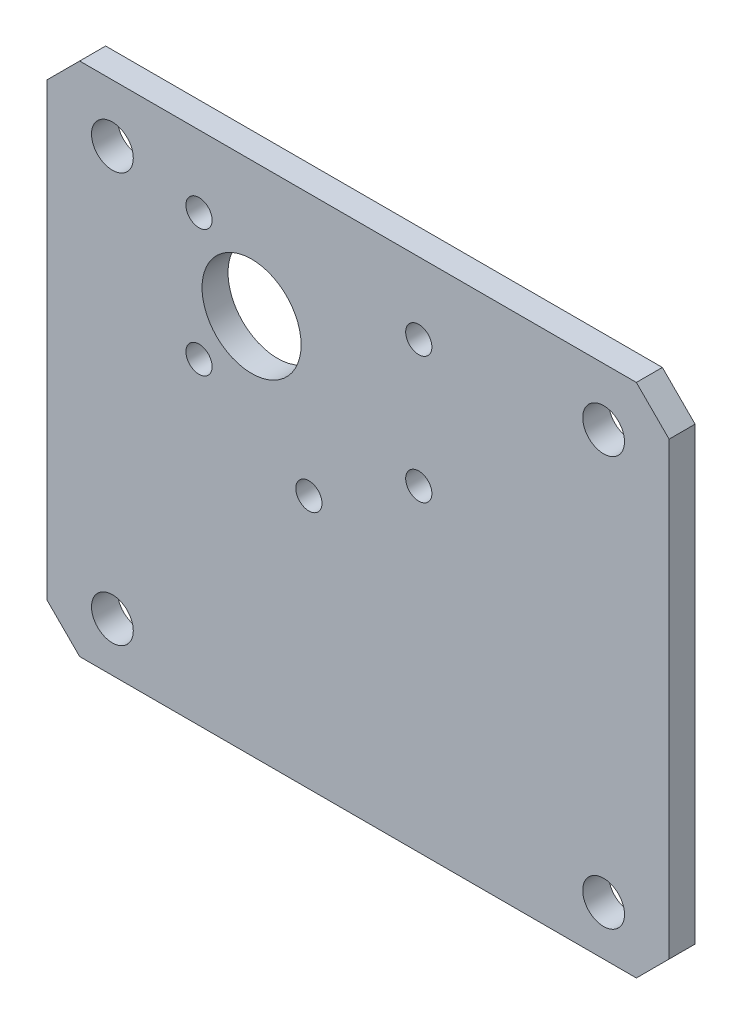
SolidWorks part; units mm, degrees
material "6061-T6 (SS)"
ref_plane "Front" through (0, 0, 0) normal (0, 0, 1) x (1, 0, 0)
ref_plane "Top" through (0, 0, 0) normal (0, 1, 0) x (1, 0, 0)
ref_plane "Right" through (0, 0, 0) normal (1, 0, 0) x (0, 0, -1)
ref_axis "side-side" through (80.9, 0, 0) along (-1, 0, 0)
ref_axis "up-down" through (0, 50, 0) along (0, -1, 0)
ref_axis "front-back" through (0, 0, -80.9) along (0, 0, 1)
sketch "Sketch1" plane through (0, 0, 0) normal (0, 0, 1) x (1, 0, 0)
  line L1 (-32, 16.5) -> (44, 16.5)
  line L2 (-32, 16.5) -> (-32, -46.5)
  line L3 (-32, -46.5) -> (44, -46.5)
  line L4 (44, 16.5) -> (44, -46.5)
  line L5 (0, -50) -> (0, 50) construction
  circle A0 centre (0, 0) radius 18.5 construction
  circle A1 centre (0, 0) radius 18.5 construction
  circle A2 centre (0, 15.5) radius 1.25 construction
  circle A3 centre (0, -15.5) radius 1.25 construction
  circle A4 centre (13.4234, -7.75) radius 1.25 construction
  circle A5 centre (13.4234, 7.75) radius 1.25 construction
  circle A6 centre (0, 15.5) radius 1.25 construction
  circle A7 centre (0, -15.5) radius 1.25 construction
  circle A8 centre (13.4234, -7.75) radius 1.25 construction
  circle A9 centre (13.4234, 7.75) radius 1.25 construction
  circle A10 centre (-13.4234, -7.75) radius 1.25 construction
  circle A11 centre (-13.4234, -7.75) radius 1.25 construction
  circle A12 centre (-13.4234, 7.75) radius 1.25 construction
  circle A13 centre (-13.4234, 7.75) radius 1.25 construction
  circle A14 centre (-7, 0) radius 6.05
  circle A15 centre (-7, 0) radius 6 construction
  circle A16 centre (-13.4234, 7.75) radius 1.6
  circle A17 centre (-13.4234, -7.75) radius 1.6
  circle A18 centre (0, -15.5) radius 1.6
  circle A19 centre (13.4234, -7.75) radius 1.6
  circle A20 centre (13.4234, 7.75) radius 1.6
  circle A21 centre (0, 15.5) radius 1.6 construction
  point P39 (-24, 9.5)
  point P40 (-24, -40.5)
  point P41 (36, 9.5)
  point P42 (36, -40.5)
  dimension "D4" = 12.1
  dimension "D5" = 3.2
  dimension "D1" = 32
  dimension "D2" = 63
  dimension "D3" = 44
extrude "Boss-Extrude1" add sketch "Sketch1" along normal blind 3.175
chamfer "Chamfer1" distance 4 angle 45 4 edges at (44, -46.5, 1.5875) (44, 16.5, 1.5875) (-32, -46.5, 1.5875) (-32, 16.5, 1.5875)
hole_wizard "1/4-20 Tapped Hole1" positions "Sketch2" profile "Sketch3" tap size "1/4-20" standard "ANSI Inch" end condition through all
sketch "Sketch2" plane through (0, 0, 3.175) normal (0, 0, 1) x (1, 0, 0)
  point P0 (-24, 9.5)
  point P3 (36, 9.5)
  point P6 (36, -40.5)
  point P9 (-24, -40.5)
sketch "Sketch3" plane through (-24, 9.5, 3.175) normal (1, 0, 0) x (0, -1, 0)
  line L0 (0, 0) -> (0, 3.175)
  line L1 (0, 3.175) -> (2.5527, 3.175)
  line L2 (2.5527, 3.175) -> (2.5527, 0)
  line L5 (2.5527, 0) -> (0, 0)
  line L11 (0, -6.35) -> (0, 107.95) construction
  dimension "Thread Major Dia." = 5.1054
  dimension "Thru Tap Drill Depth" = 3.175
